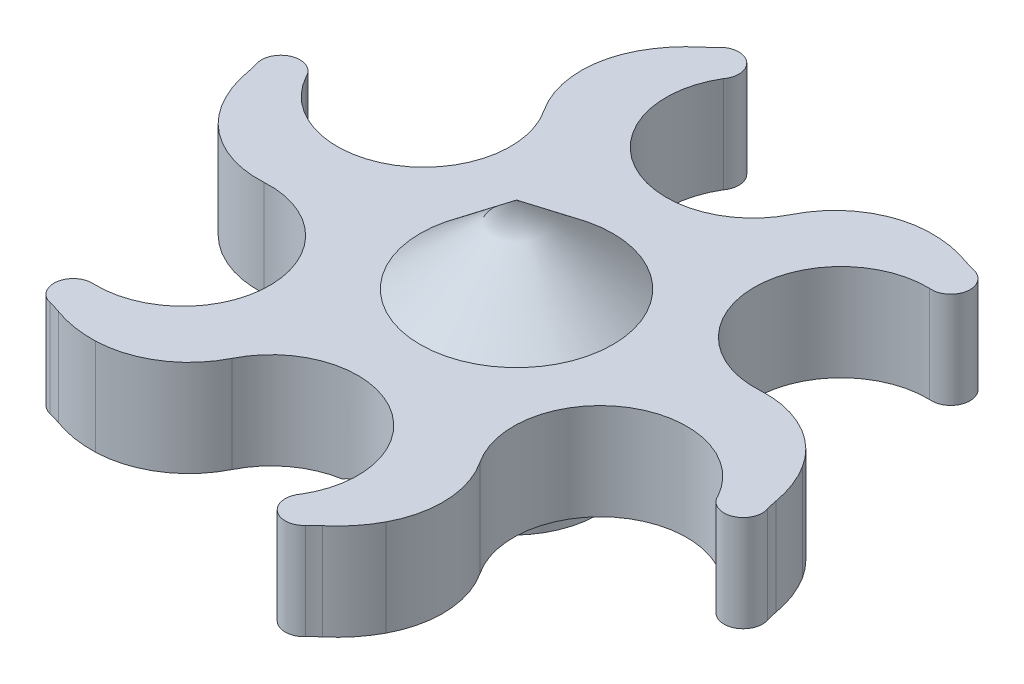
SolidWorks part; units mm, degrees
ref_plane "Front Plane" through (0, 0, 0) normal (0, 0, 1) x (1, 0, 0)
ref_plane "Top Plane" through (0, 0, 0) normal (0, 1, 0) x (1, 0, 0)
ref_plane "Right Plane" through (0, 0, 0) normal (1, 0, 0) x (0, 0, -1)
sketch "Sketch1" plane through (0, 0, 0) normal (0, 1, 0) x (1, 0, 0)
  circle A0 centre (0, 0) radius 9 construction
  arc A1 (-24.6742, 4.0231) -> (-24.6742, -4.0231) centre (0, 0) ccw
  arc A2 (-8.853, 23.38) -> (8.853, 23.38) centre (0, 25) ccw
  arc A3 (15.8212, 19.3569) -> (24.6742, 4.0231) centre (21.6506, 12.5) ccw
  arc A4 (24.6742, -4.0231) -> (15.8212, -19.3569) centre (21.6506, -12.5) ccw
  arc A5 (8.853, -23.38) -> (-8.853, -23.38) centre (0, -25) ccw
  arc A6 (-15.8212, -19.3569) -> (-24.6742, -4.0231) centre (-21.6506, -12.5) ccw
  arc A7 (-24.6742, 4.0231) -> (-15.8212, 19.3569) centre (-21.6506, 12.5) ccw
  arc A8 (-8.853, 23.38) -> (-15.8212, 19.3569) centre (0, 0) ccw
  arc A9 (15.8212, 19.3569) -> (8.853, 23.38) centre (0, 0) ccw
  arc A10 (24.6742, -4.0231) -> (24.6742, 4.0231) centre (0, 0) ccw
  arc A11 (8.853, -23.38) -> (15.8212, -19.3569) centre (0, 0) ccw
  arc A12 (-15.8212, -19.3569) -> (-8.853, -23.38) centre (0, 0) ccw
  point P18 (0, 0)
  dimension "D1" = 18
  dimension "D2" = 50
  dimension "D3" = 18
  dimension "D4" = 6
extrude "Boss-Extrude1" add sketch "Sketch1" along normal blind 10
sketch "Sketch2" plane through (0, 10, 0) normal (0, 1, 0) x (1, 0, 0)
  line L0 (0, 0) -> (-37.2267, 21.4929) construction
  line L1 (0, 0) -> (0, 42.8071) construction
  circle A0 centre (0, 25) radius 9 construction
  circle A1 centre (-21.6506, 12.5) radius 9 construction
  arc A2 (-15.8212, 19.3569) -> (-21.8212, 21.4984) centre (-21.6506, 12.5) ccw construction
  arc A3 (-22.0639, 25.4836) -> (-21.8212, 21.4984) centre (-22.0639, 23.4836) ccw construction
  arc A4 (-8.853, 23.38) -> (-22.0639, 25.4836) centre (-17.0842, 14.222) ccw construction
  arc A5 (-8.853, 23.38) -> (-15.8212, 19.3569) centre (0, 0) ccw construction
  arc A6 (-8.853, 23.38) -> (-15.8212, 19.3569) centre (0, 0) ccw construction
  arc A27 (8.853, 23.38) -> (22.0639, 25.4836) centre (17.0842, 14.222) cw
  arc A28 (22.0639, 25.4836) -> (21.8212, 21.4984) centre (22.0639, 23.4836) cw
  arc A29 (15.8212, 19.3569) -> (21.8212, 21.4984) centre (21.6506, 12.5) cw
  arc A30 (8.853, 23.38) -> (15.8212, 19.3569) centre (0, 0) cw
  arc A31 (24.6742, 4.0231) -> (33.1014, -6.3661) centre (20.8587, -7.6844) cw
  arc A32 (33.1014, -6.3661) -> (29.5287, -8.1485) centre (31.3693, -7.3661) cw
  arc A33 (24.6742, -4.0231) -> (29.5287, -8.1485) centre (21.6506, -12.5) cw
  arc A34 (24.6742, 4.0231) -> (24.6742, -4.0231) centre (0, 0) cw
  arc A35 (15.8212, -19.3569) -> (11.0375, -31.8497) centre (3.7745, -21.9063) cw
  arc A36 (11.0375, -31.8497) -> (7.7076, -29.6469) centre (9.3055, -30.8497) cw
  arc A37 (8.853, -23.38) -> (7.7076, -29.6469) centre (0, -25) cw
  arc A38 (15.8212, -19.3569) -> (8.853, -23.38) centre (0, 0) cw
  arc A39 (-8.853, -23.38) -> (-22.0639, -25.4836) centre (-17.0842, -14.222) cw
  arc A40 (-22.0639, -25.4836) -> (-21.8212, -21.4984) centre (-22.0639, -23.4836) cw
  arc A41 (-15.8212, -19.3569) -> (-21.8212, -21.4984) centre (-21.6506, -12.5) cw
  arc A42 (-8.853, -23.38) -> (-15.8212, -19.3569) centre (0, 0) cw
  arc A43 (-24.6742, -4.0231) -> (-33.1014, 6.3661) centre (-20.8587, 7.6844) cw
  arc A44 (-33.1014, 6.3661) -> (-29.5287, 8.1485) centre (-31.3693, 7.3661) cw
  arc A45 (-24.6742, 4.0231) -> (-29.5287, 8.1485) centre (-21.6506, 12.5) cw
  arc A46 (-24.6742, -4.0231) -> (-24.6742, 4.0231) centre (0, 0) cw
  arc A47 (-15.8212, 19.3569) -> (-11.0375, 31.8497) centre (-3.7745, 21.9063) cw
  arc A48 (-11.0375, 31.8497) -> (-7.7076, 29.6469) centre (-9.3055, 30.8497) cw
  arc A49 (-8.853, 23.38) -> (-7.7076, 29.6469) centre (0, 25) cw
  arc A50 (-15.8212, 19.3569) -> (-8.853, 23.38) centre (0, 0) cw
  point P55 (0, 0)
  point P63 (0, 0)
  dimension "D1" = 4
  dimension "D2" = 6
  dimension "D4" = 60
  dimension "D3" = 6
extrude "Boss-Extrude2" add sketch "Sketch2" against normal up to surface (10 mm away) up to face at (0, 0, 0)
fillet "Fillet1" radius 10 6 edges at (-24.6742, 5, 4.0231) (-8.853, 5, 23.38) (15.8212, 5, 19.3569) (24.6742, 5, -4.0231) (8.853, 5, -23.38) (-15.8212, 5, -19.3569)
sketch "Sketch3" plane through (0, 0, 0) normal (0, -1, 0) x (1, 0, 0)
  circle A0 centre (0, 0) radius 9 construction
  circle A1 centre (0, 0) radius 9
extrude "Boss-Extrude3" add sketch "Sketch3" along normal blind 6
sketch "Sketch5" plane through (0, 0, 0) normal (0, 0, 1) x (1, 0, 0)
  line L0 (-9, -6) -> (9, -6) construction
  circle A0 centre (0, -2.436) radius 1.65
  dimension "D1" = 3.3
  dimension "D2" = 3.564
extrude "Cut-Extrude1" cut sketch "Sketch5" against normal through all and the other way through all
sketch "Sketch6" plane through (0, 0, 0) normal (0, 0, 1) x (1, 0, 0)
  line L0 (0.4714, 10) -> (0.4714, 18)
  line L1 (9, 10) -> (-8.0572, 10) construction
  line L2 (0.4714, 18) -> (10.4714, 10)
  line L3 (10.4714, 10) -> (0.4714, 10)
  dimension "D1" = 10
  dimension "D2" = 8
revolve "Revolve1" add sketch "Sketch6" angle 360 about L0
ref_plane "Plane3" through (0, 0, 9) normal (0, 0, 1) x (1, 0, 0)
sketch "Sketch10" plane through (0, 0, 9) normal (0, 0, 1) x (1, 0, 0)
  circle A0 centre (0, -2.436) radius 2.85
  dimension "D1" = 5.7
extrude "Cut-Extrude4" cut sketch "Sketch10" along normal through all
mirror "Mirror1" about plane through (0, 0, 0) normal (0, 0, 1) of "Cut-Extrude4"
sketch "Sketch11" plane through (0, -6, 0) normal (0, -1, 0) x (1, 0, 0)
  line L0 (-1.8064, 2.55) -> (1.8064, 2.55)
  arc A0 (-1.8064, 2.55) -> (1.8064, 2.55) centre (0, 0) ccw
  dimension "D1" = 2.55
  dimension "D2" = 6.25
extrude "Cut-Extrude5" cut sketch "Sketch11" against normal blind 16
fillet "Fillet2" radius 10 6 edges at (-33.1014, 5, -6.3661) (-11.0375, 5, -31.8497) (22.0639, 5, -25.4836) (33.1014, 5, 6.3661) (11.0375, 5, 31.8497) (-22.0639, 5, 25.4836)
sketch "Sketch12" plane through (0, -6, 0) normal (0, -1, 0) x (1, 0, 0)
  circle A0 centre (0, 0) radius 3.5
  dimension "D1" = 7
extrude "Cut-Extrude6" cut sketch "Sketch12" against normal blind 10
